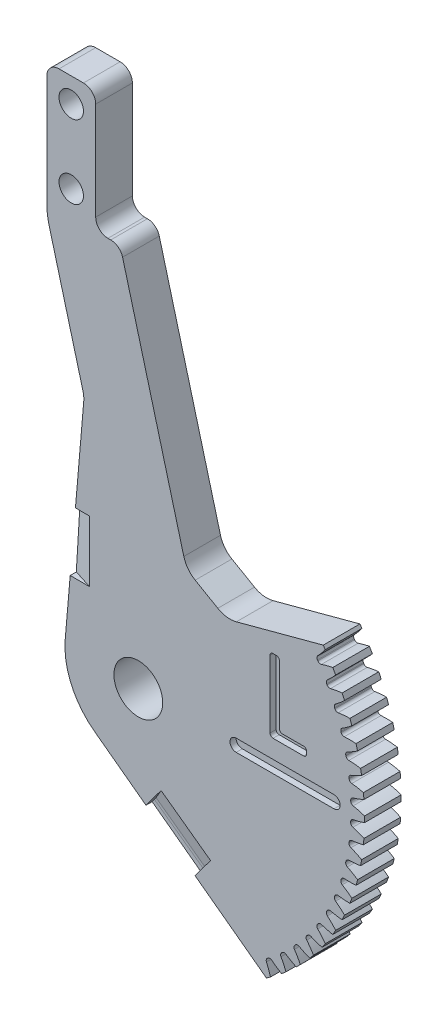
SolidWorks part; units mm, degrees
material "Delrin 2700 NC010, Low Viscosity Acetal Copolymer (SS)"
ref_plane "Front Plane" through (0, 0, 0) normal (0, 0, 1) x (1, 0, 0)
ref_plane "Top Plane" through (0, 0, 0) normal (0, 1, 0) x (1, 0, 0)
ref_plane "Right Plane" through (0, 0, 0) normal (1, 0, 0) x (0, 0, -1)
sketch "Sketch2" plane through (0, 0, 0) normal (0, 0, 1) x (1, 0, 0)
  circle A0 centre (0, 0) radius 60.325
  dimension "D1" = 120.65
extrude "Boss-Extrude2" add sketch "Sketch2" along normal mid plane 9.525
sketch "Sketch3" plane through (0, 0, 4.7625) normal (0, 0, 1) x (1, 0, 0)
  line L0 (0, 0) -> (-57.8242, 215.8028) construction
  line L1 (0, 0) -> (60.325, 0) construction
  line L2 (-14.0744, 58.6602) -> (-23.1191, 92.4153)
  line L3 (-23.1191, 92.4153) -> (-4.7182, 97.3458)
  line L4 (-4.7182, 97.3458) -> (5.2631, 60.095)
  circle A0 centre (0, 0) radius 60.325 construction
  arc A1 (5.2631, 60.095) -> (-14.0744, 58.6602) centre (0, 0) ccw
  dimension "D1" = 105
  dimension "D2" = 19.05
  dimension "D3" = 95.25
  dimension "D4" = 1.5875
extrude "Boss-Extrude3" add sketch "Sketch3" against normal up to surface (9.525 mm away) up to face at (60.325, 0, -4.7625)
sketch "Sketch4" plane through (0, 0, 4.7625) normal (0, 0, 1) x (1, 0, 0)
  line L0 (-4.7182, 97.3458) -> (-23.7682, 97.3458)
  line L1 (-23.7682, 97.3458) -> (-23.7682, 129.0958)
  line L2 (-23.7682, 129.0958) -> (-4.7182, 129.0958)
  line L3 (-4.7182, 129.0958) -> (-4.7182, 97.3458)
  line L4 (5.2631, 60.095) -> (-4.7182, 97.3458) construction
  dimension "D1" = 19.05
  dimension "D2" = 165
  dimension "D3" = 31.75
extrude "Boss-Extrude4" add sketch "Sketch4" against normal up to surface (9.525 mm away) separate body up to face at (-6.9448, 47.2448, -4.7625)
sketch "Sketch5" plane through (0, 0, 4.7625) normal (0, 0, 1) x (1, 0, 0)
  line L0 (-23.7682, 97.3458) -> (-4.7182, 97.3458) construction
  line L1 (-4.7182, 97.3458) -> (-23.1191, 92.4153) construction
  line L2 (-23.7682, 97.3458) -> (-4.7182, 97.3458)
  line L3 (-4.7182, 97.3458) -> (-23.1191, 92.4153)
  arc A0 (-23.7682, 97.3458) -> (-23.1191, 92.4153) centre (-4.7182, 97.3458) ccw
extrude "Boss-Extrude5" add sketch "Sketch5" against normal up to surface (9.525 mm away) up to face at (-6.9448, 47.2448, -4.7625)
hole_wizard "1/2 (0.5) Diameter Hole1" positions "Sketch6" profile "Sketch7" hole size "1/2" standard "ANSI Inch" end condition through all
sketch "Sketch6" plane through (0, 0, 4.7625) normal (0, 0, 1) x (1, 0, 0)
  point P0 (0, 0)
sketch "Sketch7" plane through (0, 0, 4.7625) normal (1, 0, 0) x (0, -1, 0)
  line L0 (0, 0) -> (0, 9.525)
  line L1 (0, 9.525) -> (6.3373, 9.525)
  line L2 (6.3373, 9.525) -> (6.3373, 0)
  line L5 (6.3373, 0) -> (0, 0)
  line L11 (0, -6.35) -> (0, 107.95) construction
  dimension "Thru Hole Dia." = 12.6746
  dimension "Thru Hole Depth" = 9.525
sketch "Sketch8" plane through (0, 0, 4.7625) normal (0, 0, 1) x (1, 0, 0)
  line L0 (0, 0) -> (58.2695, 15.6133) construction
  line L1 (-23.1191, 92.4153) -> (-14.0744, 58.6602) construction
  line L2 (22.9188, 27.0957) -> (49.653, 34.2591)
  line L3 (22.9188, 27.0957) -> (12.4922, 33.1155)
  line L4 (5.2631, 60.095) -> (12.4922, 33.1155)
  line L5 (5.2631, 60.095) -> (-4.7182, 97.3458) construction
  line L7 (-5.2387, 19.5509) -> (53.0308, 35.1642) construction
  arc A0 (-14.0744, 58.6602) -> (5.2631, 60.095) centre (0, 0) ccw construction
  arc A1 (49.653, 34.2591) -> (5.2631, 60.095) centre (0, 0) ccw
  dimension "D2" = 45
  dimension "D3" = 34.925
  dimension "D1" = 20.2406
extrude "Cut-Extrude1" cut sketch "Sketch8" against normal through all
sketch "Sketch9" plane through (0, 0, 4.7625) normal (0, 0, 1) x (1, 0, 0)
  line L0 (-14.0744, 58.6602) -> (-18.9799, 1.6326)
  line L1 (0, 0) -> (58.2695, 15.6133) construction
  line L2 (-23.1191, 92.4153) -> (-14.0744, 58.6602) construction
  line L3 (0, 0) -> (34.601, -49.4153) construction
  line L4 (34.601, -49.4153) -> (-11.3558, -15.2954)
  arc A0 (-18.9799, 1.6326) -> (-11.3558, -15.2954) centre (0, 0) ccw
  arc A1 (-14.0744, 58.6602) -> (49.653, 34.2591) centre (0, 0) ccw construction
  arc A2 (-14.0744, 58.6602) -> (34.601, -49.4153) centre (0, 0) ccw
  dimension "D1" = 38.1
  dimension "D2" = 70
extrude "Cut-Extrude2" cut sketch "Sketch9" against normal through all
sketch "Sketch10" plane through (0, 0, 4.7625) normal (0, 0, 1) x (1, 0, 0)
  line L0 (0, 0) -> (60.325, 0) construction
  circle A0 centre (0, 0) radius 6.3373 construction
  arc A1 (34.601, -49.4153) -> (49.653, 34.2591) centre (0, 0) ccw construction
  point P7 (58.7375, 0)
  line B0 (25.5768, -48.9104) -> (25.3948, -49.0051)
  line B1 (21.2167, -50.9534) -> (21.0271, -51.032)
  line B2 (16.695, -52.6087) -> (16.4993, -52.6704)
  line B3 (15.9333, -56.5352) -> (15.2024, -56.7361)
  line B4 (15.2024, -56.7361) -> (16.435, -61.3363)
  line B5 (44.9013, 44.9013) -> (41.5337, 41.5337)
  line B6 (41.5337, 41.5337) -> (42.0662, 40.9942)
  line B7 (40.624, 37.3642) -> (40.7627, 37.2129)
  line B8 (43.726, 33.6814) -> (43.8509, 33.5186)
  line B9 (46.4951, 29.7423) -> (46.6054, 29.5692)
  line B10 (48.9104, 25.5768) -> (49.0051, 25.3948)
  line B11 (50.9534, 21.2167) -> (51.032, 21.0271)
  line B12 (52.6087, 16.695) -> (52.6704, 16.4993)
  line B13 (53.8636, 12.0464) -> (53.908, 11.846)
  line B14 (54.7085, 7.306) -> (54.7353, 7.1025)
  line B15 (55.1371, 2.51) -> (55.146, 2.305)
  line B16 (55.146, -2.305) -> (55.1371, -2.51)
  line B17 (54.7353, -7.1025) -> (54.7085, -7.306)
  line B18 (53.908, -11.846) -> (53.8636, -12.0464)
  line B19 (52.6704, -16.4993) -> (52.6087, -16.695)
  line B20 (51.032, -21.0271) -> (50.9534, -21.2167)
  line B21 (49.0051, -25.3948) -> (48.9104, -25.5768)
  line B22 (46.6054, -29.5692) -> (46.4951, -29.7423)
  line B23 (43.8509, -33.5186) -> (43.726, -33.6814)
  line B24 (40.7627, -37.2129) -> (40.624, -37.3642)
  line B25 (37.3642, -40.624) -> (37.2129, -40.7627)
  line B26 (33.6814, -43.726) -> (33.5186, -43.8509)
  line B27 (29.7423, -46.4951) -> (29.5692, -46.6054)
  circle B28 centre (0, 0) radius 7.9375 construction
  arc B29 (28.7098, -51.2429) -> (30.0228, -50.4849) centre (0, 0) ccw
  arc B30 (26.5405, -49.0894) -> (28.7098, -51.2429) centre (43.565, -34.1095) ccw
  arc B31 (26.5405, -49.0894) -> (25.5768, -48.9104) centre (25.9446, -49.6138) ccw
  arc B32 (25.3948, -49.0051) -> (24.9887, -49.8973) centre (25.76, -49.7099) ccw
  arc B33 (25.5085, -52.9095) -> (24.9887, -49.8973) centre (2.953, -55.2508) ccw
  arc B34 (24.1345, -53.5502) -> (25.5085, -52.9095) centre (0, 0) ccw
  arc B35 (22.1611, -51.2158) -> (24.1345, -53.5502) centre (40.4264, -37.7767) ccw
  arc B36 (22.1611, -51.2158) -> (21.2167, -50.9534) centre (21.5218, -51.6862) ccw
  arc B37 (21.0271, -51.032) -> (20.5447, -51.8853) centre (21.3295, -51.7659) ccw
  arc B38 (20.8, -54.9313) -> (20.5447, -51.8853) centre (-1.8736, -55.2979) ccw
  arc B39 (19.3754, -55.4499) -> (20.8, -54.9313) centre (0, 0) ccw
  arc B40 (17.613, -52.9524) -> (19.3754, -55.4499) centre (36.9801, -41.1563) ccw
  arc B41 (17.613, -52.9524) -> (16.695, -52.6087) centre (16.9351, -53.3653) ccw
  arc B42 (16.4993, -52.6704) -> (15.9445, -53.4785) centre (16.7366, -53.4279) ccw
  arc B43 (15.9333, -56.5352) -> (15.9445, -53.4785) centre (-6.686, -54.9242) ccw
  arc B44 (16.435, -61.3363) -> (44.9013, 44.9013) centre (0, 0) ccw
  arc B45 (40.5475, 38.3415) -> (42.0662, 40.9942) centre (21.6718, 50.9087) ccw
  arc B46 (40.5475, 38.3415) -> (40.624, 37.3642) centre (41.2083, 37.9016) ccw
  arc B47 (40.7627, 37.2129) -> (41.7295, 37.0516) centre (41.3489, 37.7481) ccw
  arc B48 (44.5045, 38.3333) -> (41.7295, 37.0516) centre (52.6038, 17.1524) ccw
  arc B49 (45.479, 37.1719) -> (44.5045, 38.3333) centre (0, 0) ccw
  arc B50 (43.7349, 34.6616) -> (45.479, 37.1719) centre (26.0264, 48.8262) ccw
  arc B51 (43.7349, 34.6616) -> (43.726, 33.6814) centre (44.3548, 34.1658) ccw
  arc B52 (43.8509, 33.5186) -> (44.8, 33.2736) centre (44.4815, 34.0007) ccw
  arc B53 (47.6762, 34.3086) -> (44.8, 33.2736) centre (53.8986, 12.5024) ccw
  arc B54 (48.5457, 33.0667) -> (47.6762, 34.3086) centre (0, 0) ccw
  arc B55 (46.5895, 30.718) -> (48.5457, 33.0667) centre (30.1828, 46.3721) ccw
  arc B56 (46.5895, 30.718) -> (46.4951, 29.7423) centre (47.1638, 30.17) ccw
  arc B57 (46.6054, 29.5692) -> (47.5295, 29.2424) centre (47.2756, 29.9945) ccw
  arc B58 (50.4849, 30.0228) -> (47.5295, 29.2424) centre (54.7832, 7.7572) ccw
  arc B59 (51.2429, 28.7098) -> (50.4849, 30.0228) centre (0, 0) ccw
  arc B60 (49.0894, 26.5405) -> (51.2429, 28.7098) centre (34.1095, 43.565) ccw
  arc B61 (49.0894, 26.5405) -> (48.9104, 25.5768) centre (49.6138, 25.9446) ccw
  arc B62 (49.0051, 25.3948) -> (49.8973, 24.9887) centre (49.7099, 25.76) ccw
  arc B63 (52.9095, 25.5085) -> (49.8973, 24.9887) centre (55.2508, 2.953) ccw
  arc B64 (53.5502, 24.1345) -> (52.9095, 25.5085) centre (0, 0) ccw
  arc B65 (51.2158, 22.1611) -> (53.5502, 24.1345) centre (37.7767, 40.4264) ccw
  arc B66 (51.2158, 22.1611) -> (50.9534, 21.2167) centre (51.6862, 21.5218) ccw
  arc B67 (51.032, 21.0271) -> (51.8853, 20.5447) centre (51.7659, 21.3295) ccw
  arc B68 (54.9313, 20.8) -> (51.8853, 20.5447) centre (55.2979, -1.8736) ccw
  arc B69 (55.4499, 19.3754) -> (54.9313, 20.8) centre (0, 0) ccw
  arc B70 (52.9524, 17.613) -> (55.4499, 19.3754) centre (41.1563, 36.9801) ccw
  arc B71 (52.9524, 17.613) -> (52.6087, 16.695) centre (53.3653, 16.9351) ccw
  arc B72 (52.6704, 16.4993) -> (53.4785, 15.9445) centre (53.4279, 16.7366) ccw
  arc B73 (56.5352, 15.9333) -> (53.4785, 15.9445) centre (54.9242, -6.686) ccw
  arc B74 (56.9275, 14.4689) -> (56.5352, 15.9333) centre (0, 0) ccw
  arc B75 (54.2859, 12.9309) -> (56.9275, 14.4689) centre (44.2227, 33.2523) ccw
  arc B76 (54.2859, 12.9309) -> (53.8636, 12.0464) centre (54.6382, 12.2196) ccw
  arc B77 (53.908, 11.846) -> (54.6646, 11.2228) centre (54.6832, 12.0164) ccw
  arc B78 (57.7087, 10.9453) -> (54.6646, 11.2228) centre (54.1325, -11.4475) ccw
  arc B79 (57.972, 9.4523) -> (57.7087, 10.9453) centre (0, 0) ccw
  arc B80 (55.2064, 8.1504) -> (57.972, 9.4523) centre (46.9526, 29.2715) ccw
  arc B81 (55.2064, 8.1504) -> (54.7085, 7.306) centre (55.4953, 7.4111) ccw
  arc B82 (54.7353, 7.1025) -> (55.4347, 6.4158) centre (55.5225, 7.2047) ccw
  arc B83 (58.443, 5.874) -> (55.4347, 6.4158) centre (52.9287, -16.1219) ccw
  arc B84 (58.5752, 4.3638) -> (58.443, 5.874) centre (0, 0) ccw
  arc B85 (55.7067, 3.3078) -> (58.5752, 4.3638) centre (49.3251, 25.068) ccw
  arc B86 (55.7067, 3.3078) -> (55.1371, 2.51) centre (55.93, 2.5461) ccw
  arc B87 (55.146, 2.305) -> (55.783, 1.5599) centre (55.9391, 2.3382) ccw
  arc B88 (58.7326, 0.758) -> (55.783, 1.5599) centre (51.3222, -20.6736) ccw
  arc B89 (58.7326, -0.758) -> (58.7326, 0.758) centre (0, 0) ccw
  arc B90 (55.783, -1.5599) -> (58.7326, -0.758) centre (51.3222, 20.6736) ccw
  arc B91 (55.783, -1.5599) -> (55.146, -2.305) centre (55.9391, -2.3382) ccw
  arc B92 (55.1371, -2.51) -> (55.7067, -3.3078) centre (55.93, -2.5461) ccw
  arc B93 (58.5752, -4.3638) -> (55.7067, -3.3078) centre (49.3251, -25.068) ccw
  arc B94 (58.443, -5.874) -> (58.5752, -4.3638) centre (0, 0) ccw
  arc B95 (55.4347, -6.4158) -> (58.443, -5.874) centre (52.9287, 16.1219) ccw
  arc B96 (55.4347, -6.4158) -> (54.7353, -7.1025) centre (55.5225, -7.2047) ccw
  arc B97 (54.7085, -7.306) -> (55.2064, -8.1504) centre (55.4953, -7.4111) ccw
  arc B98 (57.972, -9.4523) -> (55.2064, -8.1504) centre (46.9526, -29.2715) ccw
  arc B99 (57.7087, -10.9453) -> (57.972, -9.4523) centre (0, 0) ccw
  arc B100 (54.6646, -11.2228) -> (57.7087, -10.9453) centre (54.1325, 11.4475) ccw
  arc B101 (54.6646, -11.2228) -> (53.908, -11.846) centre (54.6832, -12.0164) ccw
  arc B102 (53.8636, -12.0464) -> (54.2859, -12.9309) centre (54.6382, -12.2196) ccw
  arc B103 (56.9275, -14.4689) -> (54.2859, -12.9309) centre (44.2227, -33.2523) ccw
  arc B104 (56.5352, -15.9333) -> (56.9275, -14.4689) centre (0, 0) ccw
  arc B105 (53.4785, -15.9445) -> (56.5352, -15.9333) centre (54.9242, 6.686) ccw
  arc B106 (53.4785, -15.9445) -> (52.6704, -16.4993) centre (53.4279, -16.7366) ccw
  arc B107 (52.6087, -16.695) -> (52.9524, -17.613) centre (53.3653, -16.9351) ccw
  arc B108 (55.4499, -19.3754) -> (52.9524, -17.613) centre (41.1563, -36.9801) ccw
  arc B109 (54.9313, -20.8) -> (55.4499, -19.3754) centre (0, 0) ccw
  arc B110 (51.8853, -20.5447) -> (54.9313, -20.8) centre (55.2979, 1.8736) ccw
  arc B111 (51.8853, -20.5447) -> (51.032, -21.0271) centre (51.7659, -21.3295) ccw
  arc B112 (50.9534, -21.2167) -> (51.2158, -22.1611) centre (51.6862, -21.5218) ccw
  arc B113 (53.5502, -24.1345) -> (51.2158, -22.1611) centre (37.7767, -40.4264) ccw
  arc B114 (52.9095, -25.5085) -> (53.5502, -24.1345) centre (0, 0) ccw
  arc B115 (49.8973, -24.9887) -> (52.9095, -25.5085) centre (55.2508, -2.953) ccw
  arc B116 (49.8973, -24.9887) -> (49.0051, -25.3948) centre (49.7099, -25.76) ccw
  arc B117 (48.9104, -25.5768) -> (49.0894, -26.5405) centre (49.6138, -25.9446) ccw
  arc B118 (51.2429, -28.7098) -> (49.0894, -26.5405) centre (34.1095, -43.565) ccw
  arc B119 (50.4849, -30.0228) -> (51.2429, -28.7098) centre (0, 0) ccw
  arc B120 (47.5295, -29.2424) -> (50.4849, -30.0228) centre (54.7832, -7.7572) ccw
  arc B121 (47.5295, -29.2424) -> (46.6054, -29.5692) centre (47.2756, -29.9945) ccw
  arc B122 (46.4951, -29.7423) -> (46.5895, -30.718) centre (47.1638, -30.17) ccw
  arc B123 (48.5457, -33.0667) -> (46.5895, -30.718) centre (30.1828, -46.3721) ccw
  arc B124 (47.6762, -34.3086) -> (48.5457, -33.0667) centre (0, 0) ccw
  arc B125 (44.8, -33.2736) -> (47.6762, -34.3086) centre (53.8986, -12.5024) ccw
  arc B126 (44.8, -33.2736) -> (43.8509, -33.5186) centre (44.4815, -34.0007) ccw
  arc B127 (43.726, -33.6814) -> (43.7349, -34.6616) centre (44.3548, -34.1658) ccw
  arc B128 (45.479, -37.1719) -> (43.7349, -34.6616) centre (26.0264, -48.8262) ccw
  arc B129 (44.5045, -38.3333) -> (45.479, -37.1719) centre (0, 0) ccw
  arc B130 (41.7295, -37.0516) -> (44.5045, -38.3333) centre (52.6038, -17.1524) ccw
  arc B131 (41.7295, -37.0516) -> (40.7627, -37.2129) centre (41.3489, -37.7481) ccw
  arc B132 (40.624, -37.3642) -> (40.5475, -38.3415) centre (41.2083, -37.9016) ccw
  arc B133 (42.0662, -40.9942) -> (40.5475, -38.3415) centre (21.6718, -50.9087) ccw
  arc B134 (40.9942, -42.0662) -> (42.0662, -40.9942) centre (0, 0) ccw
  arc B135 (38.3415, -40.5475) -> (40.9942, -42.0662) centre (50.9087, -21.6718) ccw
  arc B136 (38.3415, -40.5475) -> (37.3642, -40.624) centre (37.9016, -41.2083) ccw
  arc B137 (37.2129, -40.7627) -> (37.0516, -41.7295) centre (37.7481, -41.3489) ccw
  arc B138 (38.3333, -44.5045) -> (37.0516, -41.7295) centre (17.1524, -52.6038) ccw
  arc B139 (37.1719, -45.479) -> (38.3333, -44.5045) centre (0, 0) ccw
  arc B140 (34.6616, -43.7349) -> (37.1719, -45.479) centre (48.8262, -26.0264) ccw
  arc B141 (34.6616, -43.7349) -> (33.6814, -43.726) centre (34.1658, -44.3548) ccw
  arc B142 (33.5186, -43.8509) -> (33.2736, -44.8) centre (34.0007, -44.4815) ccw
  arc B143 (34.3086, -47.6762) -> (33.2736, -44.8) centre (12.5024, -53.8986) ccw
  arc B144 (33.0667, -48.5457) -> (34.3086, -47.6762) centre (0, 0) ccw
  arc B145 (30.718, -46.5895) -> (33.0667, -48.5457) centre (46.3721, -30.1828) ccw
  arc B146 (30.718, -46.5895) -> (29.7423, -46.4951) centre (30.17, -47.1638) ccw
  arc B147 (29.5692, -46.6054) -> (29.2424, -47.5295) centre (29.9945, -47.2756) ccw
  arc B148 (30.0228, -50.4849) -> (29.2424, -47.5295) centre (7.7572, -54.7832) ccw
sketch_block_instance "Block1-1"
sketch_block "Block1"
extrude "Cut-Extrude3" cut sketch "Sketch10" against normal blind 12.7
sketch "Sketch15" plane through (0, 0, 4.7625) normal (0, 0, 1) x (1, 0, 0)
  line L0 (-4.7182, 129.0958) -> (-23.7682, 129.0958) construction
  line L1 (-11.0682, 129.0958) -> (-4.7182, 129.0958)
  line L2 (-11.0682, 129.0958) -> (-11.0682, 97.3458)
  line L3 (-11.0682, 97.3458) -> (-4.7182, 97.3458)
  line L4 (-4.7182, 129.0958) -> (-4.7182, 97.3458)
  line L5 (12.4922, 33.1155) -> (-4.7182, 97.3458) construction
  line L6 (-23.7682, 129.0958) -> (-23.7682, 97.3458) construction
  dimension "D1" = 12.7
  dimension "D2" = 31.75
extrude "Cut-Extrude6" cut sketch "Sketch15" against normal through all
hole_wizard "1/4 (0.25) Diameter Hole1" positions "Sketch11" profile "Sketch12" hole size "1/4" standard "ANSI Inch" end condition through all
sketch "Sketch11" plane through (0, 0, 4.7625) normal (0, 0, 1) x (1, 0, 0)
  line L0 (-17.4182, 131.8599) -> (-17.4182, 95.6738) construction
  line L4 (-23.6052, 94.8593) -> (-4.7182, 97.3458) construction
  line L8 (-11.0682, 129.0958) -> (-23.7682, 129.0958) construction
  line L9 (-11.0682, 129.0958) -> (-11.0682, 97.3458) construction
  arc A0 (-23.7682, 97.3458) -> (-23.1191, 92.4153) centre (-4.7182, 97.3458) ccw construction
  point P0 (-17.4182, 122.7458)
  point P2 (-17.4182, 103.6958)
  dimension "D1" = 19.05
  dimension "D2" = 6.35
  dimension "D3" = 6.35
sketch "Sketch12" plane through (-17.4182, 122.7458, 4.7625) normal (1, 0, 0) x (0, -1, 0)
  line L0 (0, 0) -> (0, 9.525)
  line L1 (0, 9.525) -> (3.175, 9.525)
  line L2 (3.175, 9.525) -> (3.175, 0)
  line L5 (3.175, 0) -> (0, 0)
  line L11 (0, -6.35) -> (0, 107.95) construction
  dimension "Thru Hole Dia." = 6.35
  dimension "Thru Hole Depth" = 9.525
fillet "Fillet1" radius 6.35 3 edges at (22.9188, 27.0957, 0) (12.4922, 33.1155, 0) (-14.0744, 58.6602, 0)
fillet "Fillet3" radius 3.175 4 edges at (-11.0682, 97.3458, 0) (-4.7182, 97.3458, 0) (-11.0682, 129.0958, 0) (-23.7682, 129.0958, 0)
sketch "Sketch13" plane through (0, 0, 4.7625) normal (0, 0, 1) x (1, 0, 0)
  line L0 (0, 0) -> (82.2868, 0) construction
  line L1 (25.4, 0) -> (50.8, 0) construction
  line L2 (25.4, 1.6002) -> (50.8, 1.6002)
  line L3 (25.4, -1.6002) -> (50.8, -1.6002)
  arc A0 (25.4, 1.6002) -> (25.4, -1.6002) centre (25.4, 0) ccw
  arc A1 (50.8, -1.6002) -> (50.8, 1.6002) centre (50.8, 0) ccw
  circle A2 centre (0, 0) radius 6.3373 construction
  point P5 (38.1, 0)
  dimension "D1" = 1.6002
  dimension "D3" = 25.4
  dimension "D2" = 25.4
extrude "Cut-Extrude4" cut sketch "Sketch13" against normal blind 1.5875
sketch "Sketch14" plane through (0, 0, 4.7625) normal (0, 0, 1) x (1, 0, 0)
  text T0 "<b>L</b>" font "Century Gothic" height 19.05
  dimension "D1" = 31.75
  dimension "D2" = 6.35
extrude "Cut-Extrude5" cut sketch "Sketch14" against normal blind 1.5875
fillet "Fillet2" radius 0.7937 6 edges at (43.7173, 6.35, 3.9688) (43.7173, 8.5481, 3.9688) (36.6346, 8.5481, 3.9688) (36.6346, 25.4, 3.9688) (34.1923, 6.35, 3.9688) (34.1923, 25.4, 3.9688)
sketch "Sketch16" plane through (0, 0, 4.7625) normal (0, 0, 1) x (1, 0, 0)
  line L0 (-18.9799, 1.6326) -> (-14.17, 57.5494) construction
  line L1 (-12.65, 16.6225) -> (-17.6905, 16.6225)
  line L2 (-12.65, 16.6225) -> (-12.65, 32.4975)
  line L3 (-12.65, 32.4975) -> (-17.6905, 32.4975)
  line L4 (-17.6905, 16.6225) -> (-17.6905, 32.4975)
  line L10 (5.9075, -19.9283) -> (18.7506, -29.2594)
  line L11 (18.7506, -29.2594) -> (14.7359, -34.6668)
  line L12 (14.7359, -34.6668) -> (1.9905, -25.2041)
  line L13 (1.9905, -25.2041) -> (5.9075, -19.9283)
  line L14 (33.2556, -48.4165) -> (-11.3558, -15.2954) construction
  point P7 (-12.65, 24.56)
  point P14 (1.9905, -25.2041)
  point P15 (15.945, -35.5645)
  dimension "D1" = 24.56
  dimension "D2" = 12.65
  dimension "D3" = 15.875
  dimension "D5" = 16.6225
  dimension "D4" = 126
  dimension "D7" = 12.65
extrude "Cut-Extrude7" cut sketch "Sketch16" against normal blind 1.6002
chamfer "Chamfer1" distance 1.5875 distance2 5.08 2 edges at (-12.65, 24.56, 3.1623) (12.329, -24.5938, 3.1623) first distance on face at (-12.65, 24.56, 3.9624) first distance on face at (12.329, -24.5938, 3.9624)
fillet "Fillet5" radius 3.175 1 edges at (9.3007, -28.6728, 3.1623)
equation "\"D1@Sketch2\"=2.375*2"
equation "\"D1@Sketch8\"=0.8125in-.015625"
equation "\"D3@Sketch4\"=1.250in+.125-.125"
equation "\"D1@Sketch16\"=24.56mm"
equation "\"D2@Sketch16\"=12.65mm"
equation "\"D1@Cut-Extrude7\"=9.1mm"
equation "\"D5@Sketch16\"=\"D1@Sketch16\"-\"D3@Sketch16\"/2"
equation "\"D7@Sketch16\"=\"D2@Sketch16\""
